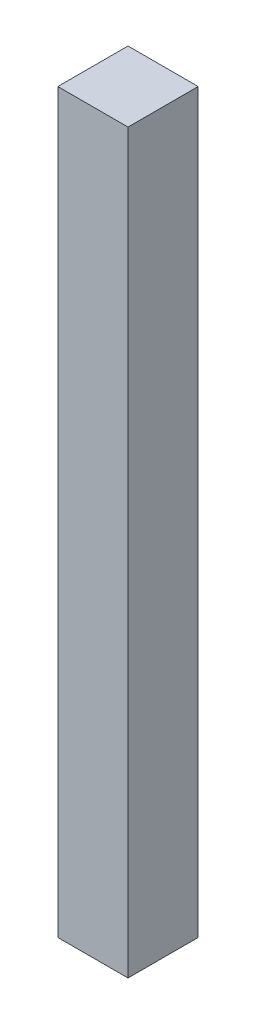
SolidWorks part; units mm, degrees
ref_plane "Front Plane" through (0, 0, 0) normal (0, 0, 1) x (1, 0, 0)
ref_plane "Top Plane" through (0, 0, 0) normal (0, 1, 0) x (1, 0, 0)
ref_plane "Right Plane" through (0, 0, 0) normal (1, 0, 0) x (0, 0, -1)
sketch "Sketch2" plane through (0, 0, 0) normal (0, 1, 0) x (1, 0, 0)
  line L1 (3, 3) -> (-3, 3)
  line L2 (3, 3) -> (3, -3)
  line L3 (3, -3) -> (-3, -3)
  line L4 (-3, 3) -> (-3, -3)
  line L5 (3, 3) -> (-3, -3) construction
  line L6 (3, -3) -> (-3, 3) construction
  point P0 (0, 0)
  dimension "D1" = 6
  dimension "D2" = 6
extrude "Boss-Extrude1" add sketch "Sketch2" along normal blind 63
